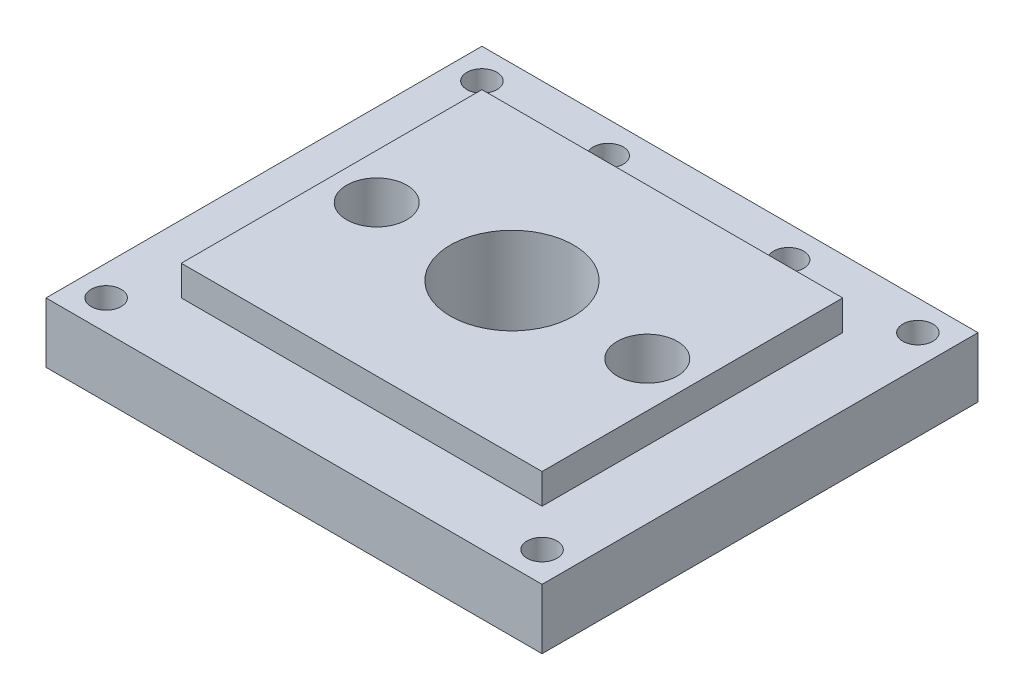
SolidWorks part; units mm, degrees
ref_plane "Front" through (0, 0, 0) normal (0, 0, 1) x (1, 0, 0)
ref_plane "Top" through (0, 0, 0) normal (0, 1, 0) x (1, 0, 0)
ref_plane "Right" through (0, 0, 0) normal (1, 0, 0) x (0, 0, -1)
sketch "草图1" plane through (0, 0, 0) normal (0, 1, 0) x (1, 0, 0)
  line L1 (8.25, -7.25) -> (-8.25, -7.25)
  line L2 (8.25, -7.25) -> (8.25, 7.25)
  line L3 (8.25, 7.25) -> (-8.25, 7.25)
  line L4 (-8.25, -7.25) -> (-8.25, 7.25)
  line L5 (8.25, -7.25) -> (-8.25, 7.25) construction
  line L6 (8.25, 7.25) -> (-8.25, -7.25) construction
  point P0 (0, 0)
  dimension "D1" = 16.5
  dimension "D2" = 14.5
extrude "凸台-拉伸1" add sketch "草图1" along normal blind 2
sketch "草图2" plane through (0, 2, 0) normal (0, 1, 0) x (1, 0, 0)
  line L1 (6, -5) -> (-6, -5)
  line L2 (6, -5) -> (6, 5)
  line L3 (6, 5) -> (-6, 5)
  line L4 (-6, -5) -> (-6, 5)
  line L5 (6, -5) -> (-6, 5) construction
  line L6 (6, 5) -> (-6, -5) construction
  point P0 (0, 0)
  dimension "D1" = 12
  dimension "D2" = 10
extrude "凸台-拉伸2" add sketch "草图2" along normal blind 1
sketch "草图3" plane through (0, 2, 0) normal (0, 1, 0) x (1, 0, 0)
  line L0 (0, 11.5253) -> (0, -10.8215) construction
  line L1 (-14.7805, 0) -> (14.0415, 0) construction
  line L2 (8.25, 7.25) -> (-8.25, 7.25) construction
  line L6 (-8.25, 7.25) -> (-8.25, -7.25) construction
  circle A0 centre (-7.25, 6.25) radius 0.5
  circle A1 centre (7.25, 6.25) radius 0.5
  circle A2 centre (7.25, -6.25) radius 0.5
  circle A3 centre (-7.25, -6.25) radius 0.5
  dimension "D1" = 1
  dimension "D3" = 1
  dimension "D2" = 1
extrude "切除-拉伸1" cut sketch "草图3" against normal through all
sketch "草图5" plane through (0, 3, 0) normal (0, 1, 0) x (1, 0, 0)
  line L0 (-11.8757, 0) -> (10.591, 0) construction
  line L1 (0, 9.9697) -> (0, -8.1643) construction
  circle A0 centre (0, 0) radius 2.05
  circle A1 centre (-4.5, 0) radius 1
  circle A2 centre (4.5, 0) radius 1
  dimension "D1" = 4.1
  dimension "D2" = 2
  dimension "D3" = 9
extrude "切除-拉伸2" cut sketch "草图5" against normal through all
sketch "草图6" plane through (0, 0, 0) normal (0, -1, 0) x (1, 0, 0)
  circle A0 centre (7.25, -6.25) radius 0.75
  circle A1 centre (-7.25, -6.25) radius 0.75
  circle A2 centre (7.25, 6.25) radius 0.75
  circle A3 centre (-7.25, 6.25) radius 0.75
  circle A4 centre (7.25, 6.25) radius 0.5 construction
  circle A5 centre (-7.25, 6.25) radius 0.5 construction
  circle A6 centre (-7.25, -6.25) radius 0.5 construction
  dimension "D1" = 1.5
extrude "切除-拉伸3" cut sketch "草图6" against normal blind 1
sketch "草图7" plane through (0, 0, 0) normal (0, -1, 0) x (1, 0, 0)
  circle A0 centre (-4.5, 0) radius 1.5
  circle A1 centre (4.5, 0) radius 1.5
  dimension "D1" = 3
  dimension "D2" = 3
extrude "切除-拉伸4" cut sketch "草图7" against normal blind 1
fillet "圆角1" radius 1 2 edges at (4.5, 1, -1.5) (-4.5, 1, -1.5)
sketch "草图8" plane through (0, 2, 0) normal (0, 1, 0) x (1, 0, 0)
  line L0 (0, 11.5957) -> (0, -8.5692) construction
  circle A0 centre (-3, 6.2) radius 0.5
  circle A1 centre (3, 6.2) radius 0.5
  dimension "D1" = 1
  dimension "D2" = 6
  dimension "D3" = 6.2
extrude "切除-拉伸5" cut sketch "草图8" against normal through all
